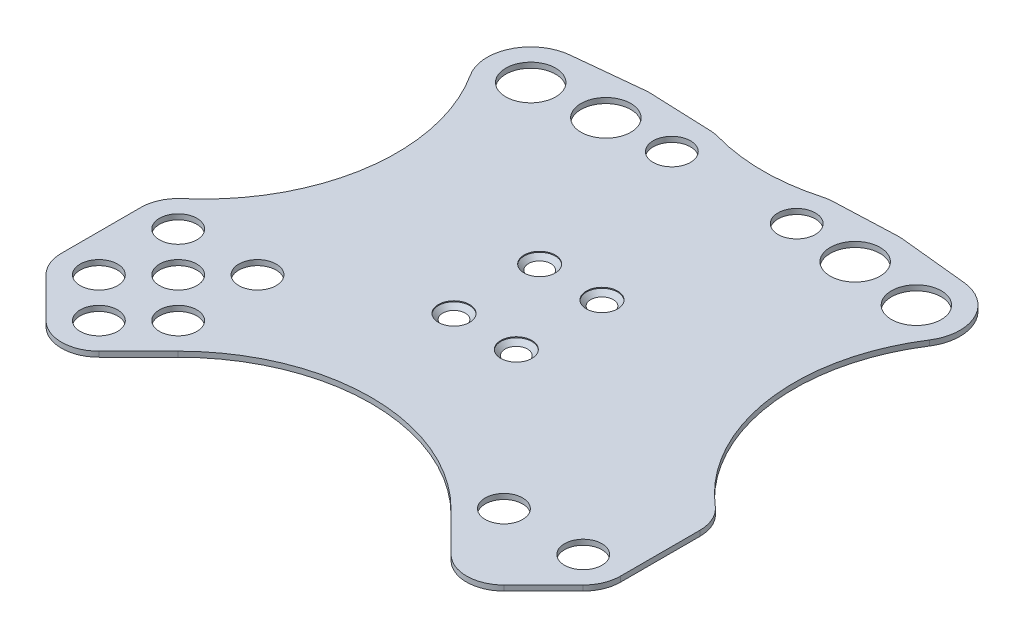
SolidWorks part; units mm, degrees
ref_plane "Front Plane" through (0, 0, 0) normal (0, 0, 1) x (1, 0, 0)
ref_plane "Top Plane" through (0, 0, 0) normal (0, 1, 0) x (1, 0, 0)
ref_plane "Right Plane" through (0, 0, 0) normal (1, 0, 0) x (0, 0, -1)
sketch "Sketch1" plane through (0, 0, 0) normal (0, 1, 0) x (1, 0, 0)
  line L0 (0, 9.3311) -> (0, -58.8842) construction
  line L1 (-10, 13.75) -> (10, 13.75)
  line L2 (-10, 13.75) -> (-10, -13.75)
  line L3 (-10, -13.75) -> (10, -13.75)
  line L4 (10, 13.75) -> (10, -13.75)
  line L5 (-10, 13.75) -> (10, -13.75) construction
  line L6 (-10, -13.75) -> (10, 13.75) construction
  line L7 (-40, 57) -> (-40, 51) construction
  line L8 (-20.0361, 60.201) -> (-20.0361, 54.201) construction
  line L9 (-63.3122, 76.6851) -> (-41.4267, 78.9271)
  line L10 (-60.4587, 48.8309) -> (-38.5733, 51.0729)
  line L11 (-18.1213, 54.3547) -> (-37.7661, 51.1794)
  line L12 (-39.439, 78.9888) -> (-19.5552, 78.1913)
  line L13 (63.3122, 76.6851) -> (41.4267, 78.9271)
  line L14 (39.439, 78.9888) -> (19.5552, 78.1913)
  line L15 (18.1213, 54.3547) -> (37.7661, 51.1794)
  line L16 (60.4587, 48.8309) -> (38.5733, 51.0729)
  line L17 (-65, -72.7279) -> (-52.2721, -60)
  line L18 (-65, -72.7279) -> (-77.7279, -60)
  line L19 (-52.2721, -60) -> (-65, -47.2721)
  line L20 (-77.7279, -60) -> (-65, -47.2721)
  line L21 (-65, -72.7279) -> (-65, -47.2721) construction
  line L22 (-52.2721, -60) -> (-77.7279, -60) construction
  line L23 (-86.2132, -51.5147) -> (-73.4853, -38.7868)
  line L24 (-56.5147, -38.7868) -> (-43.7868, -51.5147)
  line L25 (-43.7868, -68.4853) -> (-56.5147, -81.2132)
  line L26 (-86.2132, -68.4853) -> (-73.4853, -81.2132)
  line L27 (-89.7279, -60) -> (-89.7279, -34.5442)
  line L28 (-40.2721, -60) -> (-40.2721, -34.5442)
  line L29 (-77.7279, -22.5442) -> (-52.2721, -22.5442)
  line L30 (52.2721, -48) -> (77.7279, -48)
  line L31 (52.2721, -72) -> (77.7279, -72)
  line L32 (-77, -47.2721) -> (-71, -47.2721) construction
  circle A0 centre (-10, 13.75) radius 2.5
  circle A1 centre (10, 13.75) radius 2.5
  circle A2 centre (10, -13.75) radius 2.5
  circle A3 centre (-10, -13.75) radius 2.5
  circle A12 centre (0, 0) radius 27.5
  circle A13 centre (0, -433.3974) radius 500
  circle A14 centre (-40, 65) radius 8
  circle A15 centre (-40, 65) radius 14
  circle A16 centre (-61.8855, 62.758) radius 8
  circle A17 centre (-20.0361, 66.201) radius 6
  circle A18 centre (-61.8855, 62.758) radius 14
  circle A19 centre (-20.0361, 66.201) radius 12
  circle A20 centre (20.0361, 66.201) radius 6
  circle A21 centre (40, 65) radius 8
  circle A22 centre (61.8855, 62.758) radius 8
  circle A23 centre (61.8855, 62.758) radius 14
  circle A24 centre (40, 65) radius 14
  circle A25 centre (20.0361, 66.201) radius 12
  circle A26 centre (-65, -47.2721) radius 6
  circle A27 centre (-65, -47.2721) radius 12
  circle A28 centre (-77.7279, -60) radius 6
  circle A29 centre (-77.7279, -60) radius 12
  circle A30 centre (-52.2721, -60) radius 6
  circle A31 centre (-65, -72.7279) radius 6
  circle A32 centre (-65, -72.7279) radius 12
  circle A33 centre (-52.2721, -60) radius 12
  circle A34 centre (-77.7279, -34.5442) radius 6
  circle A35 centre (-52.2721, -34.5442) radius 6
  circle A36 centre (-77.7279, -34.5442) radius 12
  circle A37 centre (-52.2721, -34.5442) radius 12
  circle A38 centre (52.2721, -60) radius 6
  circle A39 centre (52.2721, -60) radius 12
  circle A40 centre (77.7279, -60) radius 12
  circle A41 centre (77.7279, -60) radius 6
  point P0 (0, 0)
  point P13 (-65, -60)
  point P27 (0, 0)
  dimension "D3" = 5
  dimension "D4" = 65
  dimension "D8" = 55
  dimension "D9" = 1000
  dimension "D10" = 16
  dimension "D12" = 6
  dimension "D13" = 12
  dimension "D1" = 20
  dimension "D2" = 27.5
  dimension "D11" = 80
  dimension "D7" = 130
  dimension "D14" = 60
extrude "Boss-Extrude1" add sketch "Sketch1" along normal blind 1.7 contours A3 L3 A2 L4 A1 L1 A0 L2 | A3 L2 A0 L1 A1 L4 A2 L3 | A12 | A19 A15 L11 | A18 L10 A15 | A18 A15 L9 | A19 L12 A15 | A24 A25 L15 | A23 A24 L16 | L13 A24 A23 | L14 A25 A24 | A33 A27 A29 A32 | A33 L24 A27 | A29 A27 L23 | A32 A29 L26 | A33 A32 L25 | A37 L29 A36 A27 | A36 L27 A29 L23 | A37 L24 A33 L28 | L31 A40 L30 A39 | A18 | A16 | A15 | A14 | A19 | A17 | A23 | A22 | A24 | A21 | A25 | A20 | A27 | A26 | A33 | A30 | A29 | A28 | A32 | A31 | A37 | A35 | A36 | A34 | A39 | A38 | A40 | A41 region at (0, 0, 0) region at (-52.2134, 0, -76.2827) region at (-29.3366, 0, -77.2452) region at (-49.672, 0, -51.4753) region at (49.672, 0, -51.4753) region at (-27.9455, 0, -54.1215) region at (52.2134, 0, -76.2827) region at (29.3366, 0, -77.2452) region at (27.9455, 0, -54.1215) region at (-65, 0, 60) region at (-50.9802, 0, 74.0198) region at (-79.0198, 0, 74.0198) region at (-49.6429, 0, 47.6698) region at (-42.8923, 0, 47.2099) region at (-80.3571, 0, 47.6698) region at (-87.1077, 0, 47.2099) region at (-65, 0, 26.0768) region at (65, 0, 60) region at (-26.7222, 0, 0)
sketch "Sketch2" plane through (0, 0, 0) normal (0, -1, 0) x (1, 0, 0)
  line L0 (0, -122.2733) -> (0, 121.7307) construction
  line L1 (-33.6698, 0) -> (48.6645, 0) construction
  line L2 (77.7279, 72) -> (52.2721, 72)
  line L3 (52.2721, 48) -> (77.7279, 48)
  line L4 (-18.1213, -54.3547) -> (-37.7661, -51.1794)
  line L5 (-77.7279, 22.5442) -> (-52.2721, 22.5442)
  line L6 (-89.7279, 60) -> (-89.7279, 34.5442)
  line L7 (-73.4853, 81.2132) -> (-86.2132, 68.4853)
  line L8 (-43.7868, 68.4853) -> (-56.5147, 81.2132)
  line L9 (-40.2721, 34.5442) -> (-40.2721, 60)
  line L10 (-77.7279, 22.5442) -> (-52.2721, 22.5442)
  line L11 (-89.7279, 60) -> (-89.7279, 34.5442)
  line L12 (-73.4853, 81.2132) -> (-86.2132, 68.4853)
  line L13 (-43.7868, 68.4853) -> (-56.5147, 81.2132)
  line L14 (-40.2721, 34.5442) -> (-40.2721, 60)
  line L15 (-39.439, -78.9888) -> (-19.5552, -78.1913)
  line L16 (-63.3122, -76.6851) -> (-41.4267, -78.9271)
  line L17 (-38.5733, -51.0729) -> (-60.4587, -48.8309)
  line L18 (-18.1213, -54.3547) -> (-37.7661, -51.1794)
  line L19 (-39.439, -78.9888) -> (-19.5552, -78.1913)
  line L20 (-63.3122, -76.6851) -> (-41.4267, -78.9271)
  line L21 (-38.5733, -51.0729) -> (-60.4587, -48.8309)
  line L22 (37.7661, -51.1794) -> (18.1213, -54.3547)
  line L23 (60.4587, -48.8309) -> (38.5733, -51.0729)
  line L24 (41.4267, -78.9271) -> (63.3122, -76.6851)
  line L25 (19.5552, -78.1913) -> (39.439, -78.9888)
  line L26 (37.7661, -51.1794) -> (18.1213, -54.3547)
  line L27 (60.4587, -48.8309) -> (38.5733, -51.0729)
  line L28 (41.4267, -78.9271) -> (63.3122, -76.6851)
  line L29 (19.5552, -78.1913) -> (39.439, -78.9888)
  line L30 (77.7279, 72) -> (52.2721, 72)
  line L31 (52.2721, 48) -> (77.7279, 48)
  line L32 (89.7279, 34.5442) -> (89.7279, 60)
  line L34 (89.7279, 60) -> (89.7279, 34.5442)
  line L35 (73.4853, 81.2132) -> (86.2132, 68.4853)
  line L36 (43.7868, 68.4853) -> (56.5147, 81.2132)
  line L37 (40.2721, 34.5442) -> (40.2721, 60)
  line L38 (77.7279, 22.5442) -> (52.2721, 22.5442)
  arc A0 (-89.7279, 34.5442) -> (-75.33, -66.6623) centre (273.1738, 34.5442) ccw
  circle A1 centre (0, 0) radius 27.5
  circle A2 centre (0, 0) radius 27.5
  arc A3 (89.7279, 34.5442) -> (75.33, -66.6623) centre (-273.1738, 34.5442) cw
  arc A4 (-19.5552, -78.1913) -> (-18.1213, -54.3547) centre (-20.0361, -66.201) ccw
  arc A5 (-89.7279, 34.5442) -> (-77.7279, 22.5442) centre (-77.7279, 34.5442) ccw
  arc A6 (-86.2132, 68.4853) -> (-89.7279, 60) centre (-77.7279, 60) ccw
  arc A7 (-56.5147, 81.2132) -> (-73.4853, 81.2132) centre (-65, 72.7279) ccw
  arc A8 (-40.2721, 60) -> (-43.7868, 68.4853) centre (-52.2721, 60) ccw
  arc A9 (-52.2721, 22.5442) -> (-40.2721, 34.5442) centre (-52.2721, 34.5442) ccw
  arc A10 (-89.7279, 34.5442) -> (-77.7279, 22.5442) centre (-77.7279, 34.5442) ccw
  arc A11 (-86.2132, 68.4853) -> (-89.7279, 60) centre (-77.7279, 60) ccw
  arc A12 (-56.5147, 81.2132) -> (-73.4853, 81.2132) centre (-65, 72.7279) ccw
  arc A13 (-40.2721, 60) -> (-43.7868, 68.4853) centre (-52.2721, 60) ccw
  arc A14 (-52.2721, 22.5442) -> (-40.2721, 34.5442) centre (-52.2721, 34.5442) ccw
  arc A15 (-41.4267, -78.9271) -> (-39.439, -78.9888) centre (-40, -65) ccw
  arc A16 (-60.4587, -48.8309) -> (-63.3122, -76.6851) centre (-61.8855, -62.758) ccw
  arc A17 (-37.7661, -51.1794) -> (-38.5733, -51.0729) centre (-40, -65) ccw
  arc A18 (-19.5552, -78.1913) -> (-18.1213, -54.3547) centre (-20.0361, -66.201) ccw
  arc A19 (-41.4267, -78.9271) -> (-39.439, -78.9888) centre (-40, -65) ccw
  arc A20 (-60.4587, -48.8309) -> (-63.3122, -76.6851) centre (-61.8855, -62.758) ccw
  arc A21 (-37.7661, -51.1794) -> (-38.5733, -51.0729) centre (-40, -65) ccw
  arc A22 (18.1213, -54.3547) -> (19.5552, -78.1913) centre (20.0361, -66.201) ccw
  arc A23 (38.5733, -51.0729) -> (37.7661, -51.1794) centre (40, -65) ccw
  arc A24 (63.3122, -76.6851) -> (60.4587, -48.8309) centre (61.8855, -62.758) ccw
  arc A25 (39.439, -78.9888) -> (41.4267, -78.9271) centre (40, -65) ccw
  arc A26 (18.1213, -54.3547) -> (19.5552, -78.1913) centre (20.0361, -66.201) ccw
  arc A27 (38.5733, -51.0729) -> (37.7661, -51.1794) centre (40, -65) ccw
  arc A28 (63.3122, -76.6851) -> (60.4587, -48.8309) centre (61.8855, -62.758) ccw
  arc A29 (39.439, -78.9888) -> (41.4267, -78.9271) centre (40, -65) ccw
  arc A30 (77.7279, 48) -> (77.7279, 72) centre (77.7279, 60) ccw
  arc A31 (52.2721, 72) -> (52.2721, 48) centre (52.2721, 60) ccw
  arc A32 (77.7279, 48) -> (77.7279, 72) centre (77.7279, 60) ccw
  arc A33 (52.2721, 72) -> (52.2721, 48) centre (52.2721, 60) ccw
  circle A34 centre (0, 112.2721) radius 61.9239
  circle A36 centre (-125.7323, -21.6725) radius 61.9239
  arc A37 (86.2132, 68.4853) -> (89.7279, 60) centre (77.7279, 60) cw
  arc A38 (56.5147, 81.2132) -> (73.4853, 81.2132) centre (65, 72.7279) cw
  arc A39 (40.2721, 60) -> (43.7868, 68.4853) centre (52.2721, 60) cw
  arc A40 (52.2721, 22.5442) -> (40.2721, 34.5442) centre (52.2721, 34.5442) cw
  arc A41 (89.7279, 34.5442) -> (77.7279, 22.5442) centre (77.7279, 34.5442) cw
  circle A42 centre (125.7323, -21.6725) radius 61.9239
  circle A43 centre (0, -137.3578) radius 61.9239
  circle M39 centre (0, 0) radius 27.5
  dimension "D1" = 0
  dimension "D2" = 0
  dimension "D3" = 0
  dimension "D4" = 0
  dimension "D5" = 0
extrude "Boss-Extrude2" add sketch "Sketch2" against normal up to surface (1.7 mm away) contours A34 A13 L14 A14 L10 A10 A0 A20 L21 A21 L18 A18 A26 L26 A27 L27 A28 A3 L32 A32 L31 A33 M39 | A41 L32 A32 L31 A33 L37 A40 L38 | A38 L36 A33 L30 A32 L35 region at (65, 0, 76.8996) region at (40.9776, 0, 64.6783) region at (65, 0, 36.5218) up to face at (10, 1.7, 16.25)
hole_wizard "CSK for M5 Flat Head Machine Screw1" positions "Sketch3" profile "Sketch4" countersink size "M5" standard "ANSI Metric"
sketch "Sketch3" plane through (0, 1.7, 0) normal (0, 1, 0) x (1, 0, 0)
  point P0 (-10, 13.75)
  point P3 (10, 13.75)
  point P6 (-10, -13.75)
  point P9 (10, -13.75)
sketch "Sketch4" plane through (-10, 1.7, -13.75) normal (1, 0, 0) x (0, 0, 1)
  line L0 (0, 0) -> (0, 6.5022)
  line L1 (0, 6.5022) -> (2.5, 5)
  line L2 (2.5, 5) -> (2.5, 2.8)
  line L3 (2.5, 2.8) -> (5, 0.3)
  line L4 (5, 0.3) -> (5, 0)
  line L6 (5, 0) -> (0, 0)
  line L7 (-2.5, 2.8) -> (-5, 0.3) construction
  line L10 (0, 6.5022) -> (-2.5, 5) construction
  line L11 (0, -6.35) -> (0, 107.95) construction
  dimension "Hole Dia." = 5
  dimension "Hole Depth" = 5
  dimension "C'Sink Dia." = 10
  dimension "C'Sink Angle" = 90
  dimension "Drill Angle" = 118
  dimension "Head Clearance" = 0.3
